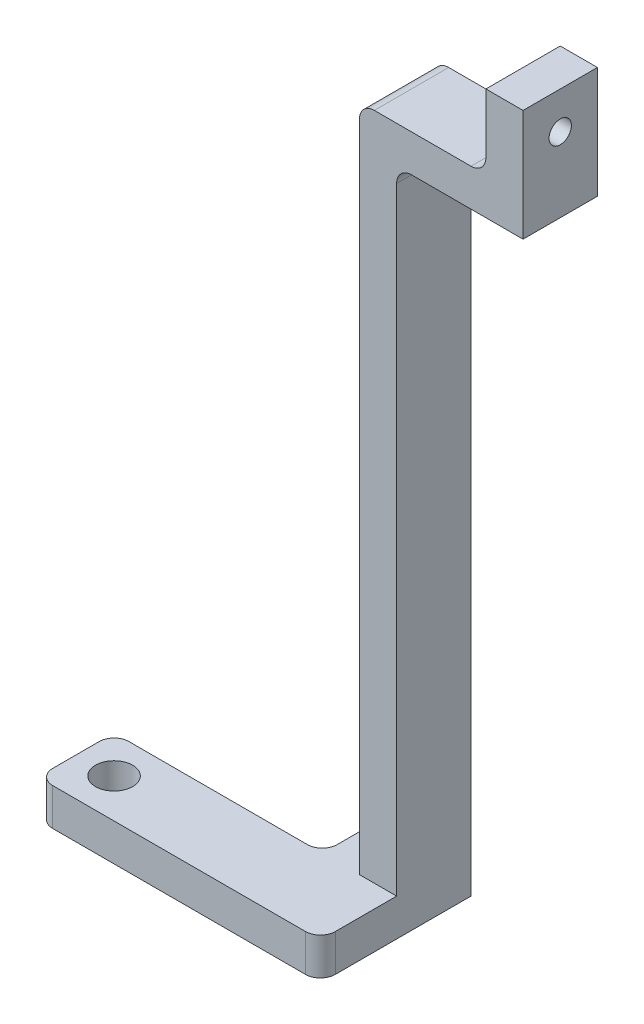
SolidWorks part; units mm, degrees
ref_plane "Front Plane" through (0, 0, 0) normal (0, 0, 1) x (1, 0, 0)
ref_plane "Top Plane" through (0, 0, 0) normal (0, 1, 0) x (1, 0, 0)
ref_plane "Right Plane" through (0, 0, 0) normal (1, 0, 0) x (0, 0, -1)
sketch "Sketch1" plane through (0, 0, 0) normal (0, 1, 0) x (1, 0, 0)
  line L0 (-8, 56.9408) -> (-8, 59.7408)
  line L1 (0, 57.5) -> (0, -57.5) construction
  line L2 (8, 56.9408) -> (8, 59.7408)
  line L3 (-6, 61.7408) -> (6, 61.7408)
  line L4 (39.4147, 47.8999) -> (47.8999, 39.4147)
  line L9 (34.6063, 45.9201) -> (36.5862, 47.8999)
  line L10 (45.9201, 34.6063) -> (47.8999, 36.5862)
  line L15 (61.7408, 6) -> (61.7408, -6)
  line L16 (56.9408, 8) -> (59.7408, 8)
  line L17 (56.9408, -8) -> (59.7408, -8)
  line L22 (47.8999, -39.4147) -> (39.4147, -47.8999)
  line L23 (45.9201, -34.6063) -> (47.8999, -36.5862)
  line L24 (34.6063, -45.9201) -> (36.5862, -47.8999)
  line L29 (6, -61.7408) -> (-6, -61.7408)
  line L30 (8, -56.9408) -> (8, -59.7408)
  line L31 (-8, -56.9408) -> (-8, -59.7408)
  line L36 (-39.4147, -47.8999) -> (-47.8999, -39.4147)
  line L37 (-34.6063, -45.9201) -> (-36.5862, -47.8999)
  line L38 (-45.9201, -34.6063) -> (-47.8999, -36.5862)
  line L43 (-61.7408, -6) -> (-61.7408, 6)
  line L44 (-56.9408, -8) -> (-59.7408, -8)
  line L45 (-56.9408, 8) -> (-59.7408, 8)
  line L50 (-47.8999, 39.4147) -> (-39.4147, 47.8999)
  line L51 (-45.9201, 34.6063) -> (-47.8999, 36.5862)
  line L52 (-34.6063, 45.9201) -> (-36.5862, 47.8999)
  arc A0 (-8, 56.9408) -> (-34.6063, 45.9201) centre (0, 0) ccw
  arc A1 (6, 61.7408) -> (8, 59.7408) centre (6, 59.7408) cw
  arc A2 (-6, 61.7408) -> (-8, 59.7408) centre (-6, 59.7408) ccw
  arc A3 (39.4147, 47.8999) -> (36.5862, 47.8999) centre (38.0005, 46.4857) ccw
  arc A4 (47.8999, 39.4147) -> (47.8999, 36.5862) centre (46.4857, 38.0005) cw
  arc A5 (61.7408, 6) -> (59.7408, 8) centre (59.7408, 6) ccw
  arc A6 (61.7408, -6) -> (59.7408, -8) centre (59.7408, -6) cw
  arc A7 (47.8999, -39.4147) -> (47.8999, -36.5862) centre (46.4857, -38.0005) ccw
  arc A8 (39.4147, -47.8999) -> (36.5862, -47.8999) centre (38.0005, -46.4857) cw
  arc A9 (6, -61.7408) -> (8, -59.7408) centre (6, -59.7408) ccw
  arc A10 (-6, -61.7408) -> (-8, -59.7408) centre (-6, -59.7408) cw
  arc A11 (-39.4147, -47.8999) -> (-36.5862, -47.8999) centre (-38.0005, -46.4857) ccw
  arc A12 (-47.8999, -39.4147) -> (-47.8999, -36.5862) centre (-46.4857, -38.0005) cw
  arc A13 (-61.7408, -6) -> (-59.7408, -8) centre (-59.7408, -6) ccw
  arc A14 (-61.7408, 6) -> (-59.7408, 8) centre (-59.7408, 6) cw
  arc A15 (-47.8999, 39.4147) -> (-47.8999, 36.5862) centre (-46.4857, 38.0005) ccw
  arc A16 (-39.4147, 47.8999) -> (-36.5862, 47.8999) centre (-38.0005, 46.4857) cw
  arc A17 (-45.9201, 34.6063) -> (-56.9408, 8) centre (0, 0) ccw
  arc A18 (-56.9408, -8) -> (-45.9201, -34.6063) centre (0, 0) ccw
  arc A19 (34.6063, 45.9201) -> (8, 56.9408) centre (0, 0) ccw
  arc A20 (-34.6063, -45.9201) -> (-8, -56.9408) centre (0, 0) ccw
  arc A21 (8, -56.9408) -> (34.6063, -45.9201) centre (0, 0) ccw
  arc A22 (45.9201, -34.6063) -> (56.9408, -8) centre (0, 0) ccw
  arc A23 (56.9408, 8) -> (45.9201, 34.6063) centre (0, 0) ccw
  point P11 (8, 61.7408)
  point P14 (-8, 61.7408)
  point P17 (-8, 58.3408)
  point P98 (0, 0)
  dimension "D1" = 115
  dimension "D2" = 2
  dimension "D3" = 16
  dimension "D4" = 2.8
  dimension "D7" = 8
extrude "Boss-Extrude1" add sketch "Sketch1" along normal blind 7
sketch "Sketch2" plane through (0, 7, 0) normal (0, 1, 0) x (1, 0, 0)
  line L0 (-57.5, 0) -> (57.5, 0) construction
  line L1 (0, 0) -> (0, 10) construction
  line L7 (17, 5) -> (22, 5)
  line L14 (0, 10) -> (29.7122, 10) construction
  line L15 (0, 10) -> (-19.5, 10) construction
  line L17 (17, 5) -> (17, 15)
  line L18 (-22, 15) -> (-17, 15)
  line L19 (-22, 15) -> (-22, 5)
  line L20 (-22, 5) -> (-17, 5)
  line L21 (-17, 15) -> (-17, 5)
  line L22 (-22, 15) -> (-17, 5) construction
  line L23 (-22, 5) -> (-17, 15) construction
  line L24 (17, 15) -> (22, 15)
  line L25 (22, 5) -> (22, 15)
  line L26 (17, 5) -> (22, 15) construction
  line L27 (17, 15) -> (22, 5) construction
  circle A0 centre (0, 0) radius 57.5 construction
  point P8 (19.5, 10)
  dimension "D1" = 10
  dimension "D2" = 17
  dimension "D3" = 17
  dimension "D4" = 10
  dimension "D5" = 5
  dimension "D6" = 10
  dimension "D7" = 5
extrude "Boss-Extrude2" add sketch "Sketch2" along normal blind 95
sketch "Sketch15" plane through (0, 0, 0) normal (0, -1, 0) x (1, 0, 0)
  circle A0 centre (0, 0) radius 3.5
  dimension "D1" = 7
extrude "Cut-Extrude3" cut sketch "Sketch15" along direction (0, 1, 0) on the side against the normal up to surface (7 mm away) contours A0 up to face at (0, 7, 0)
sketch "Sketch16" plane through (0, 0, 0) normal (0, -1, 0) x (1, 0, 0)
  line L1 (-6, 59.8) -> (6, 59.8)
  line L2 (-6, 59.8) -> (-6, 57.5)
  line L3 (-6, 57.5) -> (6, 57.5)
  line L4 (6, 59.8) -> (6, 57.5)
  point P5 (0, 57.5)
  dimension "D1" = 2.3
  dimension "D2" = 12
  dimension "D3" = 57.5
sketch "Sketch17" plane through (0, 7, 0) normal (0, 1, 0) x (1, 0, 0)
  line L0 (-6, -57.5) -> (6, -57.5) construction
  line L1 (-6, -57.5) -> (6, -57.5)
  line L2 (-6, -57.5) -> (-6, -60.5)
  line L3 (-6, -60.5) -> (6, -60.5)
  line L4 (6, -60.5) -> (6, -57.5)
  dimension "D1" = 3
ref_axis "Axis1" through (0, 107.1, 0) along (0, -1, 0)
loft "Cut-Loft2" cut profiles "Sketch16", "Sketch17" connector at (6, 0, 59.8) connector at (6, 7, 60.5)
pattern_circular "CirPattern1" count 8 over 360 about axis through (0, 107.1, 0) along (0, -1, 0) of "Cut-Loft2"
sketch "Sketch18" plane through (-17, 0, 0) normal (1, 0, 0) x (0, 0, -1)
  line L0 (15, 102) -> (15, 7) construction
  line L1 (5, 102) -> (15, 102)
  line L2 (5, 102) -> (5, 97)
  line L3 (5, 97) -> (15, 97)
  line L4 (15, 102) -> (15, 97)
  dimension "D1" = 5
extrude "Boss-Extrude3" add sketch "Sketch18" along normal up to surface (34 mm away) up to face at (17, 54.5, -10)
sketch "Sketch19" plane through (0, 0, -15) normal (0, 0, -1) x (-1, 0, 0)
  line L0 (-17, 93) -> (-11.0447, 92.2688)
  line L1 (-17, 97) -> (-17, 7) construction
  line L4 (-11, 91) -> (-19.8185, 91) construction
  line L5 (-17, 89) -> (-11.0447, 89.7312)
  line L6 (-17, 93) -> (-17, 89)
  arc A1 (-11.0447, 92.2688) -> (-11.0447, 89.7312) centre (-11.2005, 91) cw
  dimension "D1" = 6
  dimension "D4" = 4
  dimension "D2" = 7
  dimension "D3" = 4
extrude "Boss-Extrude4" add sketch "Sketch19" against normal blind 10
fillet "Fillet1" radius 2 2 edges at (17, 93, -10) (17, 89, -10)
fillet "Fillet2" radius 2 4 edges at (-22, 102, -10) (22, 102, -10) (-17, 97, -10) (17, 97, -10)
pattern_linear "LPattern2" count 10 spacing 8 along (0, -1, 0) of "Fillet1", "Boss-Extrude4"
sketch "Sketch20" plane through (0, 7, 0) normal (0, 1, 0) x (1, 0, 0)
  line L0 (0, 0) -> (0, 50) construction
  circle A0 centre (0, 50) radius 2.5
  dimension "D2" = 5
  dimension "D1" = 50
extrude "Cut-Extrude4" cut sketch "Sketch20" against normal blind 10
pattern_circular "CirPattern2" count 4 over 360 about axis through (0, 107.1, 0) along (0, -1, 0) of "Cut-Extrude4"
sketch "Sketch21" plane through (0, 0, 0) normal (1, 0, 0) x (0, 0, -1)
  line L1 (67.451, 109.7761) -> (-68.4979, 109.7761)
  line L2 (67.451, 109.7761) -> (67.451, 0)
  line L3 (67.451, 0) -> (-68.4979, 0)
  line L4 (-68.4979, 109.7761) -> (-68.4979, 0)
  dimension "D1" = 109.7761
  dimension "D2" = 135.9489
  dimension "D3" = 68.4979
extrude "Cut-Extrude5" cut sketch "Sketch21" along normal up to surface (61.7408 mm away) up to face at (61.7408, 3.5, 0)
sketch "Sketch22" plane through (0, 7, 0) normal (0, 1, 0) x (1, 0, 0)
  line L1 (-17, 5) -> (-53, 5)
  line L2 (-17, 5) -> (-17, -3.2506)
  line L3 (-19, -5.2506) -> (-53, -5.2506)
  line L4 (-55, 3) -> (-55, -3.2506)
  circle A0 centre (-50, 0) radius 2.5 construction
  circle A1 centre (-50, 0) radius 2.5
  arc A2 (-19, -5.2506) -> (-17, -3.2506) centre (-19, -3.2506) ccw
  arc A3 (-55, 3) -> (-53, 5) centre (-53, 3) cw
  arc A4 (-53, -5.2506) -> (-55, -3.2506) centre (-53, -3.2506) cw
  point P10 (-17, -5.2506)
  point P15 (-55, -5.2506)
  dimension "D3" = 2
  dimension "D1" = 38
  dimension "D2" = 10.2506
extrude "Boss-Extrude5" add sketch "Sketch22" along normal blind 5
sketch "Sketch23" plane through (0, 7, 0) normal (0, 1, 0) x (1, 0, 0)
  line L25 (0, 60.5) -> (0, 61.7408)
  line L26 (0, 61.7408) -> (-6, 61.7408)
  line L27 (-8, 59.7408) -> (-8, 56.9408)
  line L28 (-34.6063, 45.9201) -> (-36.5862, 47.8999)
  line L29 (-39.4147, 47.8999) -> (-47.8999, 39.4147)
  line L30 (-47.8999, 36.5862) -> (-45.9201, 34.6063)
  line L31 (-56.9408, 8) -> (-59.7408, 8)
  line L32 (-61.7408, 6) -> (-61.7408, -6)
  line L33 (-59.7408, -8) -> (-56.9408, -8)
  line L34 (-45.9201, -34.6063) -> (-47.8999, -36.5862)
  line L35 (-47.8999, -39.4147) -> (-39.4147, -47.8999)
  line L36 (-36.5862, -47.8999) -> (-34.6063, -45.9201)
  line L37 (-8, -56.9408) -> (-8, -59.7408)
  line L38 (-6, -61.7408) -> (0, -61.7408)
  line L39 (0, -61.7408) -> (0, -60.5)
  line L40 (0, -60.5) -> (-6, -60.5)
  line L41 (-6, -60.5) -> (-6, -57.5)
  line L42 (-6, -57.5) -> (0, -57.5)
  line L43 (0, -57.5) -> (0, -52.5)
  line L44 (0, -47.5) -> (0, -3.5)
  line L45 (0, 3.5) -> (0, 47.5)
  line L46 (0, 52.5) -> (0, 57.5)
  line L47 (0, 57.5) -> (-6, 57.5)
  line L48 (-6, 57.5) -> (-6, 60.5)
  line L49 (-6, 60.5) -> (0, 60.5)
  line L50 (0, 60.5) -> (0, 61.7408)
  line L51 (0, 61.7408) -> (-6, 61.7408)
  line L52 (-8, 59.7408) -> (-8, 56.9408)
  line L53 (-34.6063, 45.9201) -> (-36.5862, 47.8999)
  line L54 (-39.4147, 47.8999) -> (-47.8999, 39.4147)
  line L55 (-47.8999, 36.5862) -> (-45.9201, 34.6063)
  line L56 (-56.9408, 8) -> (-59.7408, 8)
  line L57 (-61.7408, 6) -> (-61.7408, -6)
  line L58 (-59.7408, -8) -> (-56.9408, -8)
  line L59 (-45.9201, -34.6063) -> (-47.8999, -36.5862)
  line L60 (-47.8999, -39.4147) -> (-39.4147, -47.8999)
  line L61 (-36.5862, -47.8999) -> (-34.6063, -45.9201)
  line L62 (-8, -56.9408) -> (-8, -59.7408)
  line L63 (-6, -61.7408) -> (0, -61.7408)
  line L64 (0, -61.7408) -> (0, -60.5)
  line L65 (0, -60.5) -> (-6, -60.5)
  line L66 (-6, -60.5) -> (-6, -57.5)
  line L67 (-6, -57.5) -> (0, -57.5)
  line L68 (0, -57.5) -> (0, -52.5)
  line L69 (0, -47.5) -> (0, -3.5)
  line L70 (0, 3.5) -> (0, 47.5)
  line L71 (0, 52.5) -> (0, 57.5)
  line L72 (0, 57.5) -> (-6, 57.5)
  line L73 (-6, 57.5) -> (-6, 60.5)
  line L74 (-6, 60.5) -> (0, 60.5)
  arc A15 (-6, 61.7408) -> (-8, 59.7408) centre (-6, 59.7408) ccw
  arc A16 (-8, 56.9408) -> (-34.6063, 45.9201) centre (0, 0) ccw
  arc A17 (-36.5862, 47.8999) -> (-39.4147, 47.8999) centre (-38.0005, 46.4857) ccw
  arc A18 (-47.8999, 39.4147) -> (-47.8999, 36.5862) centre (-46.4857, 38.0005) ccw
  arc A19 (-45.9201, 34.6063) -> (-56.9408, 8) centre (0, 0) ccw
  arc A20 (-59.7408, 8) -> (-61.7408, 6) centre (-59.7408, 6) ccw
  arc A21 (-61.7408, -6) -> (-59.7408, -8) centre (-59.7408, -6) ccw
  arc A22 (-56.9408, -8) -> (-45.9201, -34.6063) centre (0, 0) ccw
  arc A23 (-47.8999, -36.5862) -> (-47.8999, -39.4147) centre (-46.4857, -38.0005) ccw
  arc A24 (-39.4147, -47.8999) -> (-36.5862, -47.8999) centre (-38.0005, -46.4857) ccw
  arc A25 (-34.6063, -45.9201) -> (-8, -56.9408) centre (0, 0) ccw
  arc A26 (-8, -59.7408) -> (-6, -61.7408) centre (-6, -59.7408) ccw
  arc A27 (0, -47.5) -> (0, -52.5) centre (0, -50) ccw
  arc A28 (0, 3.5) -> (0, -3.5) centre (0, 0) ccw
  arc A29 (0, 52.5) -> (0, 47.5) centre (0, 50) ccw
  arc A30 (-6, 61.7408) -> (-8, 59.7408) centre (-6, 59.7408) ccw
  arc A31 (-8, 56.9408) -> (-34.6063, 45.9201) centre (0, 0) ccw
  arc A32 (-36.5862, 47.8999) -> (-39.4147, 47.8999) centre (-38.0005, 46.4857) ccw
  arc A33 (-47.8999, 39.4147) -> (-47.8999, 36.5862) centre (-46.4857, 38.0005) ccw
  arc A34 (-45.9201, 34.6063) -> (-56.9408, 8) centre (0, 0) ccw
  arc A35 (-59.7408, 8) -> (-61.7408, 6) centre (-59.7408, 6) ccw
  arc A36 (-61.7408, -6) -> (-59.7408, -8) centre (-59.7408, -6) ccw
  arc A37 (-56.9408, -8) -> (-45.9201, -34.6063) centre (0, 0) ccw
  arc A38 (-47.8999, -36.5862) -> (-47.8999, -39.4147) centre (-46.4857, -38.0005) ccw
  arc A39 (-39.4147, -47.8999) -> (-36.5862, -47.8999) centre (-38.0005, -46.4857) ccw
  arc A40 (-34.6063, -45.9201) -> (-8, -56.9408) centre (0, 0) ccw
  arc A41 (-8, -59.7408) -> (-6, -61.7408) centre (-6, -59.7408) ccw
  arc A42 (0, -47.5) -> (0, -52.5) centre (0, -50) ccw
  arc A43 (0, 3.5) -> (0, -3.5) centre (0, 0) ccw
  arc A44 (0, 52.5) -> (0, 47.5) centre (0, 50) ccw
  dimension "D1" = 0
extrude "Cut-Extrude6" cut sketch "Sketch23" against normal blind 10
sketch "Sketch24" plane through (0, 0, 60.5) normal (0, 0, 1) x (1, 0, 0)
  line L4 (0, 0) -> (0, 7)
  line L5 (0, 7) -> (-6, 7)
  line L6 (-6, 7) -> (-6, 0)
  line L7 (-6, 0) -> (0, 0)
  line L8 (0, 0) -> (0, 7)
  line L9 (0, 7) -> (-6, 7)
  line L10 (-6, 7) -> (-6, 0)
  line L11 (-6, 0) -> (0, 0)
  dimension "D1" = 0
extrude "Cut-Extrude7" cut sketch "Sketch24" against normal blind 1
sketch "Sketch25" plane through (0, 0, -60.5) normal (0, 0, -1) x (-1, 0, 0)
  line L4 (6, 0) -> (6, 7)
  line L5 (6, 7) -> (0, 7)
  line L6 (0, 7) -> (0, 0)
  line L7 (0, 0) -> (6, 0)
  line L8 (6, 0) -> (6, 7)
  line L9 (6, 7) -> (0, 7)
  line L10 (0, 7) -> (0, 0)
  line L11 (0, 0) -> (6, 0)
  dimension "D1" = 0
extrude "Cut-Extrude8" cut sketch "Sketch25" against normal blind 1
sketch "Sketch26" plane through (-22, 0, 0) normal (-1, 0, 0) x (0, 0, 1)
  line L0 (-15, 100) -> (-15, 7) construction
  line L1 (-5, 7) -> (-15, 7)
  line L2 (-5, 7) -> (-5, 12)
  line L3 (-5, 12) -> (-15, 12)
  line L4 (-15, 7) -> (-15, 12)
  point P7 (0, 0)
extrude "Boss-Extrude6" add sketch "Sketch26" along normal blind 5
sketch "Sketch27" plane through (0, 102, 0) normal (0, 1, 0) x (1, 0, 0)
  line L0 (0, 15) -> (-20, 15) construction
  line L1 (0, 5) -> (-5, 5)
  line L2 (0, 5) -> (0, 15)
  line L3 (0, 15) -> (-5, 15)
  line L4 (-5, 5) -> (-5, 15)
  dimension "D1" = 5
extrude "Boss-Extrude7" add sketch "Sketch27" along normal blind 10
sketch "Sketch29" plane through (-5, 0, 0) normal (-1, 0, 0) x (0, 0, 1)
  line L0 (-5, 112) -> (-15, 102) construction
  circle A0 centre (-10, 107) radius 1.5
  dimension "D1" = 3
extrude "Cut-Extrude9" cut sketch "Sketch29" against normal up to surface (5 mm away) up to face at (0, 104.5, -10)
fillet "Fillet3" radius 2 3 edges at (-27, 9.5, -5) (-5, 102, -10) (-27, 9.5, -15)
equation "\"85.00.00mm\"=8500"
